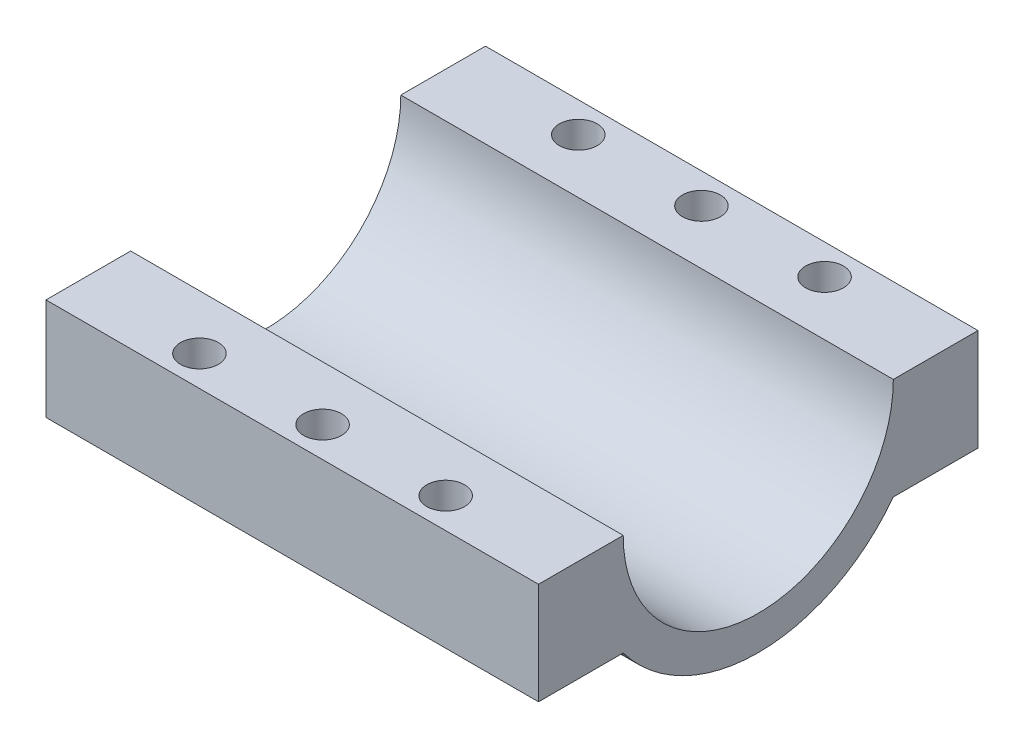
SolidWorks part; units mm, degrees
ref_plane "Front Plane" through (0, 0, 0) normal (0, 0, 1) x (1, 0, 0)
ref_plane "Top Plane" through (0, 0, 0) normal (0, 1, 0) x (1, 0, 0)
ref_plane "Right Plane" through (0, 0, 0) normal (1, 0, 0) x (0, 0, -1)
sketch "Sketch1" plane through (0, 0, 0) normal (0, 1, 0) x (1, 0, 0)
  line L0 (-40.0608, 0) -> (47.511, 0) construction
  line L1 (-32.5, -29) -> (32.5, -29)
  line L2 (-32.5, -29) -> (-32.5, 29)
  line L3 (-32.5, 29) -> (32.5, 29)
  line L4 (32.5, -29) -> (32.5, 29)
  line L5 (-32.5, -29) -> (32.5, 29) construction
  line L6 (-32.5, 29) -> (32.5, -29) construction
  line L7 (-32.5, 25) -> (32.5, 25) construction
  line L8 (-32.5, 18.075) -> (32.5, 18.075) construction
  line L9 (-32.5, -25) -> (32.5, -25) construction
  line L10 (-32.5, -18.075) -> (32.5, -18.075) construction
  line L11 (0, -29) -> (0, 29) construction
  circle A0 centre (-16.25, 25) radius 2.5
  circle A1 centre (16.25, 25) radius 2.5
  circle A2 centre (16.25, -25) radius 2.5
  circle A3 centre (-16.25, -25) radius 2.5
  circle A4 centre (0, 25) radius 2.5
  circle A5 centre (0, -25) radius 2.5
  point P0 (0, 0)
  dimension "D3" = 5
  dimension "D4" = 5
  dimension "D9" = 5
  dimension "D10" = 5
  dimension "D1" = 65
  dimension "D2" = 58
  dimension "D5" = 16.25
  dimension "D6" = 16.25
  dimension "D7" = 18.075
  dimension "D8" = 4
extrude "Boss-Extrude1" add sketch "Sketch1" along normal blind 22.325
sketch "Sketch2" plane through (32.5, 0, 0) normal (1, 0, 0) x (0, 0, -1)
  line L0 (-29, 22.325) -> (29, 22.325) construction
  line L1 (-29, 22.325) -> (-17.825, 22.325) construction
  line L2 (-17.825, 22.325) -> (-17.825, 0) construction
  line L3 (-29, 0) -> (29, 0) construction
  line L4 (29, 22.325) -> (17.825, 22.325) construction
  line L5 (17.825, 22.325) -> (17.825, 0) construction
  line L6 (-17.825, 8.8835) -> (-29, 8.8835)
  line L7 (-29, 22.325) -> (-29, 0) construction
  line L11 (29, 22.325) -> (29, 0) construction
  line L12 (29, 8.8835) -> (17.825, 8.8835)
  line L13 (0, -12.8013) -> (0, 49.7133) construction
  line L14 (-29, 8.8835) -> (-29, -2.8834)
  line L15 (-29, -2.8834) -> (29, -2.8834)
  line L16 (29, -2.8834) -> (29, 8.8835)
  circle A0 centre (0, 22.325) radius 17.825
  arc A1 (-17.825, 8.8835) -> (17.825, 8.8835) centre (0, 22.325) ccw
  dimension "D2" = 35.65
  dimension "D1" = 0
  dimension "D3" = 11.7669
extrude "Cut-Extrude1" cut sketch "Sketch2" against normal through all
sketch "Sketch3" plane through (0, 8.8835, 0) normal (0, -1, 0) x (1, 0, 0)
  circle A0 centre (-16.25, -25) radius 6
  circle A1 centre (0, -25) radius 6
  circle A2 centre (16.25, -25) radius 6
  circle A3 centre (16.25, 25) radius 6
  circle A4 centre (0, 25) radius 6
  circle A5 centre (-16.25, 25) radius 6
  dimension "D1" = 12
  dimension "D2" = 12
  dimension "D3" = 12
  dimension "D4" = 12
  dimension "D5" = 12
  dimension "D6" = 12
